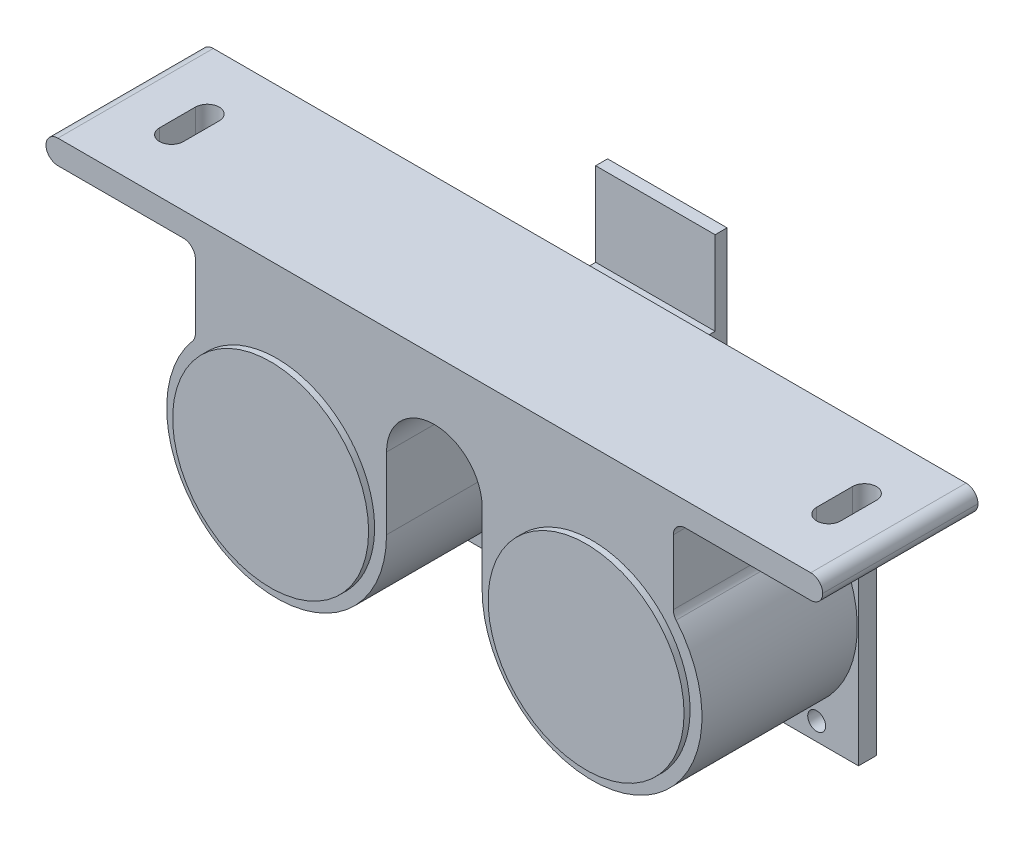
SolidWorks part; units mm, degrees
other "Sensor Mount"
other "Sensor"
ref_plane "Front Plane" through (0, 0, 0) normal (0, 0, 1) x (1, 0, 0)
ref_plane "Top Plane" through (0, 0, 0) normal (0, 1, 0) x (1, 0, 0)
ref_plane "Right Plane" through (0, 0, 0) normal (1, 0, 0) x (0, 0, -1)
sketch "Sketch1" plane through (0, 0, 0) normal (0, 0, 1) x (1, 0, 0)
  line L0 (9.3, 10) -> (0, 10) construction
  line L1 (0, 0) -> (45, 0)
  line L2 (0, 0) -> (0, 20)
  line L3 (0, 20) -> (45, 20)
  line L4 (45, 0) -> (45, 20)
  line L5 (35.7, 10) -> (45, 10) construction
  line L6 (27.5, 10) -> (27.5, 0) construction
  line L7 (17.5, 10) -> (17.5, 0) construction
  circle A0 centre (9.3, 10) radius 8.2
  circle A1 centre (35.7, 10) radius 8.2
  circle A2 centre (1.5, 1.5) radius 0.75
  circle A3 centre (1.5, 18.5) radius 0.75
  circle A4 centre (41.5, 18.5) radius 0.75
  circle A5 centre (41.5, 1.5) radius 0.75
  point P11 (0, 10)
  dimension "D3" = 16.4
  dimension "D6" = 1.5
  dimension "D1" = 20
  dimension "D2" = 45
  dimension "D4" = 10
  dimension "D7" = 40
  dimension "D8" = 1.5
  dimension "D9" = 1.5
  dimension "D10" = 1.5
extrude "Boss-Extrude1" add sketch "Sketch1" against normal blind 1.5 contours L1 L4 L3 L2 A5 A4 A3 A2 A1 A0 | A1 | A0 region at (22.515, 10, 0) region at (35.7, 10, 0)
extrude "Boss-Extrude2" add sketch "Sketch1<3>" along normal blind 13.5 contours A0 | A1 region at (9.3, 10, 0) region at (35.7, 10, 0)
sketch "Sketch1<3>" plane through (0, 0, 0) normal (0, 0, 1) x (1, 0, 0) same geometry as "Sketch1"
sketch "Sketch2" plane through (0, 20, 0) normal (0, 1, 0) x (1, 0, 0)
  line L0 (0, 1.5) -> (45, 1.5) construction
  line L1 (17.5, 6.5) -> (27.5, 6.5)
  line L2 (17.5, 6.5) -> (17.5, 1.5)
  line L3 (17.5, 1.5) -> (27.5, 1.5)
  line L4 (27.5, 6.5) -> (27.5, 1.5)
  line L5 (22.5, 1.5) -> (22.5, 6.5) construction
  line L6 (17.5, 5.5) -> (27.5, 5.5)
  line M8 (45, 1.5) -> (0, 1.5)
  dimension "D1" = 10
  dimension "D2" = 5
  dimension "D3" = 1
extrude "Boss-Extrude3" add sketch "Sketch2" against normal blind 3 contours L5 L4 L6 M8 | L3 L5 L6 L2 | L6 L5 L1 L2 | L5 L6 L4 L1 region at (20, 20, -6) region at (25, 20, -6) region at (20, 20, -3.5) region at (25, 20, -3.5)
extrude "Boss-Extrude4" add sketch "Sketch2<3>" along normal blind 7 contours L5 L6 L4 L1 | L6 L5 L1 L2 region at (20, 20, -6) region at (25, 20, -6)
sketch "Sketch2<3>" plane through (0, 20, 0) normal (0, 1, 0) x (1, 0, 0) same geometry as "Sketch2"
sketch "Sketch4" plane through (0, 0, 0) normal (0, 0, 1) x (1, 0, 0)
  line L0 (0, 20) -> (45, 20) construction
  line L1 (18.5, 10) -> (18.5, 16)
  line L2 (55, 25) -> (-10, 25)
  line L3 (26.5, 16) -> (26.5, 10)
  line L5 (-10, 25) -> (-10, 23)
  line L6 (-10, 23) -> (2.5, 23)
  line L7 (2.5, 23) -> (2.5, 16.1968)
  line L8 (22.5, 20) -> (22.5, 16) construction
  line L9 (42.5, 23) -> (42.5, 16.1968)
  line L10 (55, 23) -> (42.5, 23)
  line L11 (55, 25) -> (55, 23)
  circle A0 centre (35.7, 10) radius 8.2 construction
  circle A1 centre (9.3, 10) radius 8.2 construction
  circle A2 centre (35.7, 10) radius 8.2
  circle A3 centre (9.3, 10) radius 8.2
  arc A4 (2.5, 16.1968) -> (18.5, 10) centre (9.3, 10) ccw
  arc A5 (26.5, 10) -> (42.5, 16.1968) centre (35.7, 10) ccw
  arc A6 (26.5, 16) -> (18.5, 16) centre (22.5, 16) ccw
  circle A7 centre (9.3, 10) radius 9.2 construction
  circle A8 centre (35.7, 10) radius 9.2 construction
  point P17 (2.0154, 21.7843)
  point P20 (42.5, 24.9817)
  point P21 (55.9056, 23)
  point P25 (42.5, 23.304)
  point P26 (0, 0)
  point P29 (48.3947, 20.6607)
  dimension "D2" = 2
  dimension "D3" = 65
  dimension "D4" = 40
  dimension "D5" = 3
  dimension "D1" = 1
extrude "Boss-Extrude5" add sketch "Sketch4" along normal blind 13 separate body
sketch "Sketch5" plane through (0, 25, 0) normal (0, 1, 0) x (1, 0, 0)
  line L0 (55, -6.5) -> (-10, -6.5) construction
  line L1 (-10, -13) -> (-10, 0) construction
  line L3 (55, -13) -> (55, 0) construction
  line L4 (-4.5, -5) -> (-4.5, -8) construction
  line L5 (-3.5, -5) -> (-3.5, -8)
  line L6 (-5.5, -5) -> (-5.5, -8)
  line L7 (50.5, -5) -> (50.5, -8) construction
  line L8 (51.5, -5) -> (51.5, -8)
  line L9 (49.5, -5) -> (49.5, -8)
  line L10 (55, 0) -> (-10, 0) construction
  line L11 (-10, -13) -> (-10, 0) construction
  arc A2 (-3.5, -5) -> (-5.5, -5) centre (-4.5, -5) ccw
  arc A3 (-5.5, -8) -> (-3.5, -8) centre (-4.5, -8) ccw
  arc A4 (51.5, -5) -> (49.5, -5) centre (50.5, -5) ccw
  arc A5 (49.5, -8) -> (51.5, -8) centre (50.5, -8) ccw
  point P1 (-4.5, -6.5)
  point P13 (50.5, -6.5)
  point P20 (-4.8625, -6.5)
  point P21 (50.6806, -6.5)
  dimension "D1" = 1
  dimension "D4" = 4.5
  dimension "D2" = 5
  dimension "D3" = 4.5
extrude "Cut-Extrude1" cut sketch "Sketch5" against normal up to next (2 mm away)
fillet "Fillet1" radius 1 8 edges at (55, 25, 6.5) (-10, 25, 6.5) (42.5, 16.1968, 6.5) (2.5, 16.1968, 6.5) (42.5, 23, 6.5) (55, 23, 6.5) (2.5, 23, 6.5) (-10, 23, 6.5)
